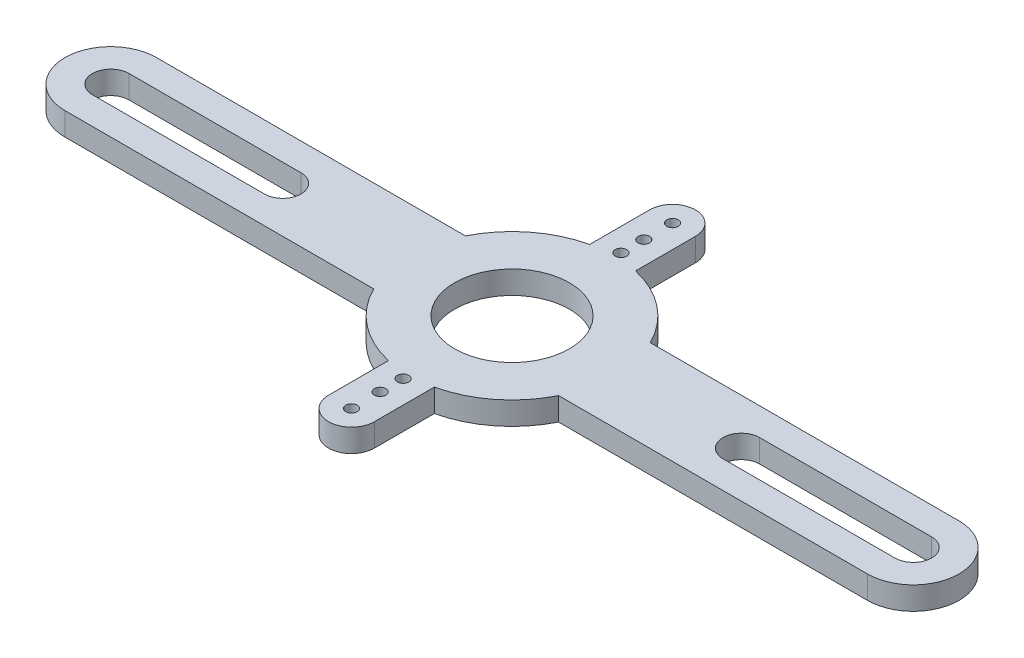
SolidWorks part; units mm, degrees
ref_plane "Front Plane" through (0, 0, 0) normal (0, 0, 1) x (1, 0, 0)
ref_plane "Top Plane" through (0, 0, 0) normal (0, 1, 0) x (1, 0, 0)
ref_plane "Right Plane" through (0, 0, 0) normal (1, 0, 0) x (0, 0, -1)
sketch "Sketch1" plane through (0, 0, 0) normal (0, 1, 0) x (1, 0, 0)
  line L1 (0, 3) -> (70, 3)
  line L2 (0, -3) -> (70, -3)
  circle A0 centre (0, 0) radius 1.6
  arc A1 (0, 3) -> (0, -3) centre (0, 0) ccw
  circle A2 centre (70, 0) radius 1.6
  arc A3 (70, -3) -> (70, 3) centre (70, 0) ccw
  circle A4 centre (35, 0) radius 1.6
extrude "Boss-Extrude1" add sketch "Sketch1" along normal blind 2
sketch "Sketch2" plane through (0, 2, 0) normal (0, 1, 0) x (1, 0, 0)
  line L0 (35, 0) -> (38.2578, 0)
  line L1 (37, -3) -> (33, -3)
  line L2 (37, -14) -> (37, -3)
  line L3 (33, 14) -> (33, 3)
  line L4 (70, 3) -> (0, 3) construction
  line L5 (37, 14) -> (37, 3)
  line L6 (37, 3) -> (33, 3)
  line L7 (33, -14) -> (33, -3)
  circle A0 centre (35, 9.5) radius 0.5
  arc A1 (37, 14) -> (33, 14) centre (35, 14) ccw
  circle A2 centre (35, 14) radius 0.5
  circle A3 centre (35, 11.5) radius 0.5
  circle A4 centre (35, -11.5) radius 0.5
  circle A5 centre (35, -14) radius 0.5
  arc A6 (37, -14) -> (33, -14) centre (35, -14) cw
  circle A7 centre (35, -9.5) radius 0.5
  circle M1 centre (70, 0) radius 1.6
  arc M2 (0, 3) -> (0, -3) centre (0, 0) ccw
  line M3 (0, -3) -> (70, -3)
  arc M4 (70, -3) -> (70, 3) centre (70, 0) ccw
  line M5 (70, 3) -> (0, 3)
  circle M6 centre (0, 0) radius 1.6
  circle M7 centre (35, 0) radius 1.6
extrude "Boss-Extrude2" add sketch "Sketch2" against normal up to surface (2 mm away) contours L5 A1 L3 A3 A2 A0 M5 | A6 L2 L7 A5 A4 A7 M3 | M5 M2 M3 M4 M7 M6 M1 region at (36.864, 2, 8.5) region at (35, 2, 2.2376) region at (35, 2, -3.136) up to face at (35, 0, 0)
sketch "Sketch3" plane through (0, 0, 0) normal (0, -1, 0) x (-1, 0, 0)
  circle A0 centre (-70, 0) radius 1.6
  circle A1 centre (0, 0) radius 1.6
extrude "Boss-Extrude3" add sketch "Sketch3" against normal blind 4
sketch "Sketch4" plane through (0, 2, 0) normal (0, 1, 0) x (1, 0, 0)
  circle A0 centre (0, 0) radius 1.5
  circle A1 centre (70, 0) radius 1.5
  circle A2 centre (70, 0) radius 5.6181
  circle A3 centre (0, 0) radius 9.0195
extrude "Cut-Extrude1" cut sketch "Sketch4" along normal blind 20
sketch "Sketch5" plane through (0, 2, 0) normal (0, 1, 0) x (1, 0, 0)
  line L1 (55, 1.6) -> (70, 1.6)
  line L2 (0, -1.6) -> (15, -1.6)
  line L3 (70, -1.6) -> (55, -1.6)
  line L4 (15, 1.6) -> (0, 1.6)
  arc A0 (70, -1.6) -> (70, 1.6) centre (70, 0) ccw
  arc A1 (55, 1.6) -> (55, -1.6) centre (55, 0) ccw
  arc A2 (15, 1.6) -> (15, -1.6) centre (15, 0) cw
  arc A3 (0, -1.6) -> (0, 1.6) centre (0, 0) cw
extrude "Cut-Extrude2" cut sketch "Sketch5" against normal blind 10 and the other way blind 10
sketch "Sketch6" plane through (0, 2, 0) normal (0, 1, 0) x (1, 0, 0)
  line L0 (0, 4) -> (70, 4)
  line L2 (70, -4) -> (0, -4)
  line L4 (0, -3) -> (70, -3)
  line L6 (70, 3) -> (0, 3)
  line L7 (70, -3) -> (0, -3)
  arc A0 (0, 3) -> (0, -3) centre (0, 0) ccw
  arc A1 (0, 4) -> (0, -4) centre (0, 0) ccw
  arc A3 (70, -4) -> (70, 4) centre (70, 0) ccw
  arc A4 (70, -3) -> (70, 3) centre (70, 0) ccw
  line M13 (33, 3) -> (0, 3)
  arc M14 (0, 3) -> (0, -3) centre (0, 0) ccw
  line M15 (0, -3) -> (33, -3)
  line M16 (33, -3) -> (33, -14)
  line M18 (37, -14) -> (37, -3)
  line M19 (37, -3) -> (70, -3)
  arc M20 (70, -3) -> (70, 3) centre (70, 0) ccw
  line M21 (70, 3) -> (37, 3)
  line M22 (37, 3) -> (37, 14)
  arc M23 (37, 14) -> (33, 14) centre (35, 14) ccw
  line M24 (33, 14) -> (33, 3)
  circle M26 centre (35, 9.5) radius 0.5
  circle M27 centre (35, 14) radius 0.5
  circle M28 centre (35, 11.5) radius 0.5
extrude "Boss-Extrude5" add sketch "Sketch6" against normal up to surface (2 mm away) contours L6 L0 M22 M24 | L0 A1 L2 M16 M15 M14 M13 M24 | L2 A3 L0 M22 M21 M20 M19 M18 | L4 L2 M16 M18 | L0 M24 M22 M23 M26 M28 M27 region at (16.5, 2, -3.6215) region at (33.1265, 2, -9) region at (35, 2, -3.5) region at (53.5, 2, -3.6215) region at (35, 2, 3.5) up to face at (7.5, 0, 0)
sketch "Sketch7" plane through (0, 2, 0) normal (0, 1, 0) x (1, 0, 0)
  circle A0 centre (35, 0) radius 5
  circle A2 centre (35, 0) radius 9
extrude "Boss-Extrude6" add sketch "Sketch7" against normal up to surface (2 mm away) up to face at (35, 0, 0)
sketch "Sketch8" plane through (0, 2, 0) normal (0, 1, 0) x (1, 0, 0)
  circle A0 centre (35, 0) radius 5
extrude "Cut-Extrude3" cut sketch "Sketch8" against normal blind 10
